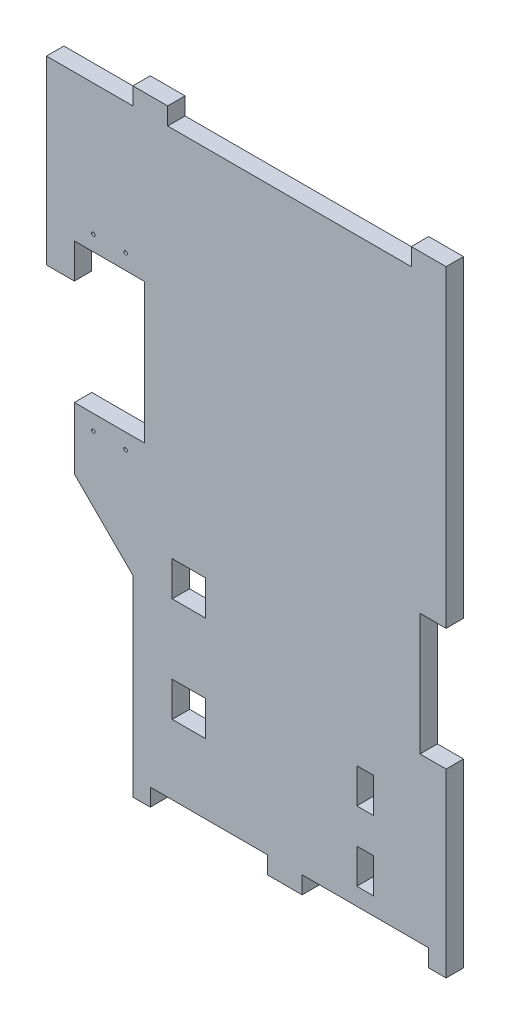
SolidWorks part; units mm, degrees
material "Balsa"
ref_plane "Plan de face" through (0, 0, 0) normal (0, 0, 1) x (1, 0, 0)
ref_plane "Plan de dessus" through (0, 0, 0) normal (0, 1, 0) x (1, 0, 0)
ref_plane "Plan de droite" through (0, 0, 0) normal (1, 0, 0) x (0, 0, -1)
sketch "Esquisse1" plane through (0, 0, 0) normal (0, 0, 1) x (1, 0, 0)
  line L0 (90, 82) -> (90, 167)
  line L1 (5, 0) -> (90, 0)
  line L2 (0, 0) -> (0, 167)
  line L3 (10, 167) -> (80, 167)
  line L4 (90, 0) -> (90, 47)
  line L5 (90, 82) -> (82.5, 82)
  line L6 (0, 167) -> (0, 172)
  line L7 (0, 172) -> (10, 172)
  line L8 (10, 167) -> (10, 172)
  line L9 (0, 0) -> (0, -5)
  line L10 (90, 167) -> (90, 172)
  line L11 (90, 172) -> (80, 172)
  line L12 (80, 167) -> (80, 172)
  line L13 (0, -5) -> (5, -5)
  line L14 (5, 0) -> (5, -5)
  line L15 (64.3348, 35) -> (64.3348, 25)
  line L16 (90, 47) -> (82.5, 47)
  line L17 (82.5, 82) -> (82.5, 47)
  line L18 (64.3348, 35) -> (69.1423, 35)
  line L19 (64.3348, 25) -> (69.1423, 25)
  line L20 (69.1423, 35) -> (69.1423, 25)
  line L21 (71.3405, 35) -> (66.533, 35) construction
  line L22 (64.3348, 35) -> (64.3348, 25) construction
  line L23 (69.1423, 35) -> (69.1423, 25) construction
  line L24 (18.5374, 30) -> (3.1837, 30) construction
  line L25 (64.3348, 15) -> (69.1423, 15)
  line L26 (64.3348, 15) -> (64.3348, 5)
  line L27 (64.3348, 5) -> (69.1423, 5)
  line L28 (69.1423, 15) -> (69.1423, 5)
  line L29 (11.3034, 30) -> (20.8832, 30)
  line L30 (11.3034, 30) -> (11.3034, 20)
  line L31 (11.3034, 20) -> (20.8832, 20)
  line L32 (20.8832, 30) -> (20.8832, 20)
  line L33 (3.1837, 20) -> (18.5374, 20) construction
  line L36 (21.1471, 30) -> (5.7933, 30) construction
  line L37 (11.3034, 60) -> (20.8832, 60)
  line L38 (11.3034, 60) -> (11.3034, 50)
  line L39 (11.3034, 50) -> (20.8832, 50)
  line L40 (20.8832, 60) -> (20.8832, 50)
  dimension "D1" = 167
  dimension "D2" = 90
  dimension "D3" = 10
  dimension "D4" = 5
  dimension "D5" = 5
  dimension "D6" = 7.5
  dimension "D7" = 35
  dimension "D8" = 82
  dimension "D9" = 10
  dimension "D10" = 10
  dimension "D11" = 10
extrude "Boss.-Extru.1" add sketch "Esquisse1" along normal blind 5
sketch "Esquisse2" plane through (0, 0, 5) normal (0, 0, 1) x (1, 0, 0)
  line L0 (0, 172) -> (0, -5) construction
  line L1 (0, 167) -> (-16.8145, 167)
  line L2 (0, 167) -> (0, 50.1855)
  line L3 (0, 50.1855) -> (-16.8145, 67)
  line L4 (-16.8145, 167) -> (-16.8145, 67)
  line L6 (80, 167) -> (10, 167) construction
  dimension "D1" = 16.8145
  dimension "D2" = 135
  dimension "D3" = 100
extrude "Boss.-Extru.2" add sketch "Esquisse2" against normal blind 5
sketch "Esquisse3" plane through (0, 0, 5) normal (0, 0, 1) x (1, 0, 0)
  line L0 (0, 167) -> (-16.8145, 167) construction
  line L1 (3.3855, 125) -> (-16.8145, 125)
  line L2 (3.3855, 125) -> (3.3855, 84.8)
  line L3 (3.3855, 84.8) -> (-16.8145, 84.8)
  line L4 (-16.8145, 125) -> (-16.8145, 84.8)
  line L5 (-16.8145, 167) -> (-16.8145, 67) construction
  dimension "D1" = 42
  dimension "D2" = 20.2
  dimension "D3" = 40.2
extrude "Enlèv. mat.-Extru.1" cut sketch "Esquisse3" against normal blind 5
sketch "Esquisse4" plane through (0, 0, 5) normal (0, 0, 1) x (1, 0, 0)
  line L0 (5, 0) -> (90, 0) construction
  line L1 (-16.8145, 167) -> (-24.8145, 167)
  line L2 (-16.8145, 167) -> (-16.8145, 115)
  line L3 (-16.8145, 115) -> (-24.8145, 115)
  line L4 (-24.8145, 167) -> (-24.8145, 115)
  line L5 (38.6337, 0) -> (48.6337, 0)
  line L6 (38.6337, 0) -> (38.6337, -5)
  line L7 (38.6337, -5) -> (48.6337, -5)
  line L8 (48.6337, 0) -> (48.6337, -5)
  line L9 (92.5017, -5) -> (-34.7153, -5) construction
  line L10 (90, 0) -> (90, 47) construction
  line L11 (90, 0) -> (85, 0)
  line L12 (90, 0) -> (90, -5)
  line L13 (90, -5) -> (85, -5)
  line L14 (85, 0) -> (85, -5)
  line L16 (0, 50.1855) -> (0, -5) construction
  dimension "D1" = 8
  dimension "D2" = 52
  dimension "D3" = 5
  dimension "D4" = 5
  dimension "D5" = 10
  dimension "D6" = 38.6337
extrude "Boss.-Extru.3" add sketch "Esquisse4" against normal blind 5
sketch "Esquisse5" plane through (0, 0, 5) normal (0, 0, 1) x (1, 0, 0)
  circle A0 centre (-11.3395, 129.4) radius 0.5
  circle A1 centre (-2.0895, 129.4) radius 0.5
  circle A2 centre (-11.3395, 80.4) radius 0.5
  circle A3 centre (-2.0895, 80.4) radius 0.5
  dimension "D1" = 1
extrude "Enlèv. mat.-Extru.2" cut sketch "Esquisse5" against normal blind 5
